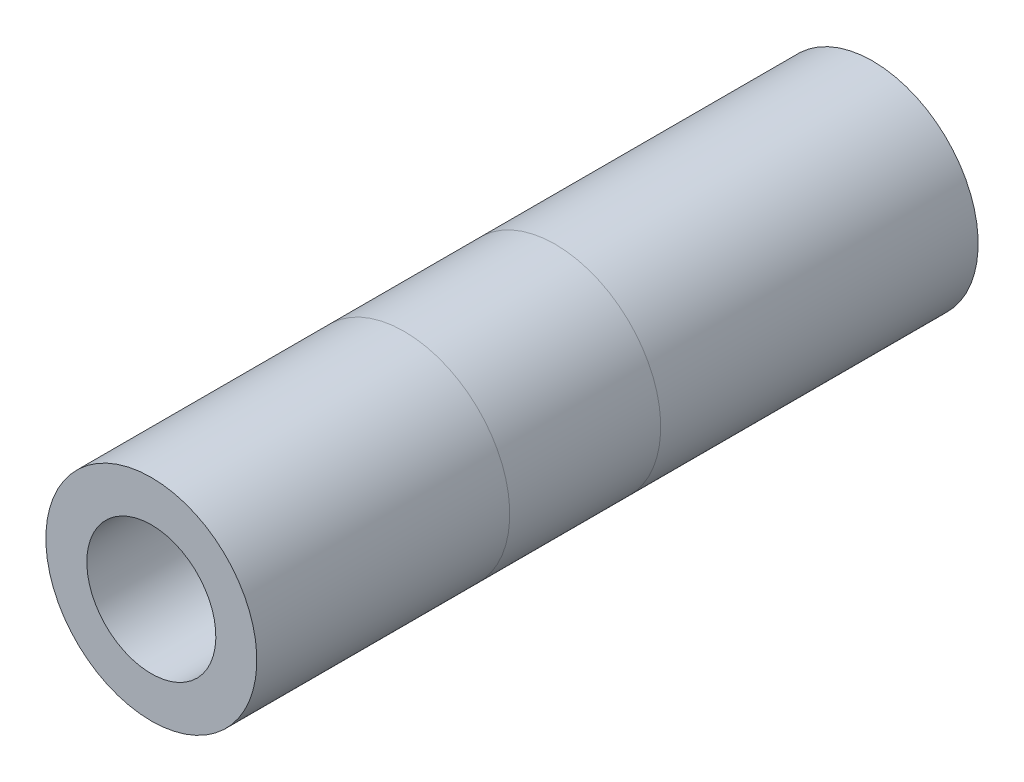
SolidWorks part; units mm, degrees
material "Silicon Rubber"
ref_plane "X-Y Datum" through (0, 0, 0) normal (0, 0, 1) x (1, 0, 0)
ref_plane "X-Z Datum" through (0, 0, 0) normal (0, 1, 0) x (1, 0, 0)
ref_plane "Y-Z Datum" through (0, 0, 0) normal (1, 0, 0) x (0, 0, -1)
sketch3d "3DSketch1"
  line L0 (-46.03, 0, -24.6) -> (-46.03, 0, 0)
  line L1 (-46.03, 0, 0) -> (-46.03, 0, 11.7)
  line L2 (-46.03, 0, 31.3016) -> (-46.03, 0, 11.7)
  arc A0 (-42.0547, 0, 0) -> (-50.0053, 0, 0) centre (-46.03, 0, 0) ccw construction
  arc A1 (-42.0547, 0, 0) -> (-50.0053, 0, 0) centre (-46.03, 0, 0) ccw construction
  arc A2 (-46.03, 5, -24.6) -> (-41.03, 0, -24.6) centre (-46.03, 0, -24.6) ccw construction
  arc A3 (-46.03, 5, -24.6) -> (-41.03, 0, -24.6) centre (-46.03, 0, -24.6) ccw construction
  circle A4 centre (-46.03, 0, 11.7) radius 6.1071 construction
  circle A5 centre (-46.03, 0, 11.7) radius 6.1071 construction
  circle A6 centre (-46.03, 0, 31.3016) radius 6.5 construction
  circle A7 centre (-46.03, 0, 31.3016) radius 6.5 construction
  point P3 (-46.03, 0, 3.9753)
  point P4 (-46.03, 0, 3.9753)
  point P8 (-46.03, 0, -29.6)
  point P9 (-46.03, 0, -29.6)
  point P12 (-46.03, 0, 5.593)
  point P14 (-46.03, 0, 5.593)
  point P17 (-46.03, 0, 24.8016)
  point P19 (-46.03, 0, 24.8016)
sweep "Sweep1" add path "3DSketch1" circular profile diameter 16.35 parameters "D3"=16.35
sweep "Cut-Sweep1" cut path "3DSketch1<2>" circular profile diameter 10 parameters "D3"=10
sketch3d "3DSketch1<2>" same geometry as "3DSketch1"
sketch3d "3DSketch2"
  circle A1 centre (-46.03, 0, 0) radius 5 construction
  circle A2 centre (-46.03, 0, 0) radius 5 construction
  circle A3 centre (-46.03, 0, 11.7) radius 5 construction
  circle A5 centre (-46.03, 0, 11.7) radius 5 construction
  point P2 (-46.03, 0, -5)
  point P4 (-46.03, 0, -5)
  point P9 (-46.03, 0, 6.7)
  point P12 (-46.03, 0, 6.7)
